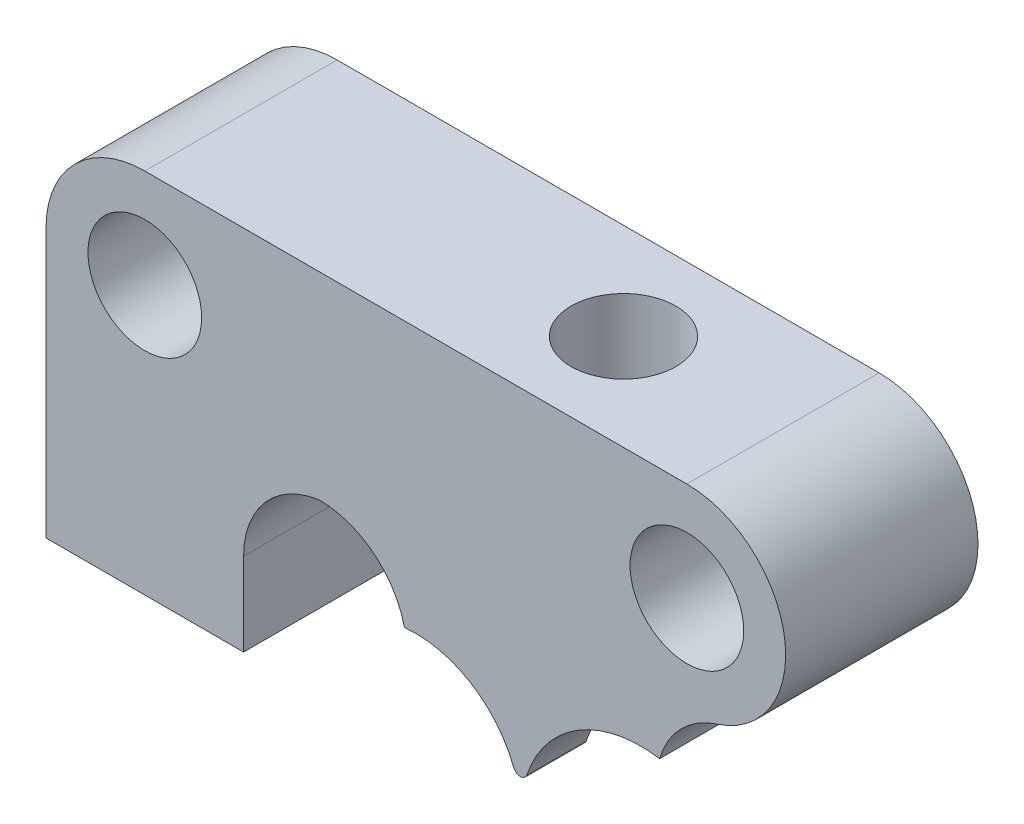
SolidWorks part; units mm, degrees
ref_plane "Front Plane" through (0, 0, 0) normal (0, 0, 1) x (1, 0, 0)
ref_plane "Top Plane" through (0, 0, 0) normal (0, 1, 0) x (1, 0, 0)
ref_plane "Right Plane" through (0, 0, 0) normal (1, 0, 0) x (0, 0, -1)
sketch "Sketch1" plane through (0, 0, 0) normal (0, 0, 1) x (1, 0, 0)
  line L0 (0, 0) -> (-15.5, 0) construction
  line L1 (0, 0) -> (0, -15.5) construction
  line L2 (-15.5, 0) -> (15.5, 0) construction
  line L3 (-15.5, 5.65) -> (15.5, 5.65)
  line L4 (-15.5, -5.65) -> (15.5, -5.65)
  circle A0 centre (-15.5, 0) radius 1.6
  circle A1 centre (15.5, 0) radius 1.6
  arc A2 (-15.5, 5.65) -> (-15.5, -5.65) centre (-15.5, 0) ccw
  arc A3 (15.5, -5.65) -> (15.5, 5.65) centre (15.5, 0) ccw
  point P7 (0, 0)
  point P12 (-21.15, 0)
  point P13 (21.15, 0)
  dimension "D4" = 3.2
  dimension "D1" = 15.5
  dimension "D2" = 15.5
  dimension "D3" = 42.3
extrude "Boss-Extrude1" add sketch "Sketch1" along normal blind 5.5 and the other way blind 5.5
sketch "Sketch3" plane through (0, 0, 0) normal (0, 0, 1) x (1, 0, 0)
  line L0 (0, 0) -> (0, -15.5) construction
  line L1 (6.375, 5.65) -> (6.375, -22.8049) construction
  line L2 (15.5, 5.65) -> (-15.5, 5.65) construction
  circle A0 centre (0, -15.5) radius 5.5
  circle A1 centre (12.85, -15.5) radius 6.3
  dimension "D2" = 11
  dimension "D3" = 1.05
  dimension "D4" = 12.6
  dimension "D6" = 0.875
  dimension "D1" = 15.5
  dimension "D5" = 12.85
sketch "Sketch4" plane through (0, 5.65, 0) normal (0, 1, 0) x (1, 0, 0)
  circle A0 centre (6.375, 0) radius 3
  dimension "D1" = 6
extrude "Cut-Extrude2" cut sketch "Sketch4" against normal blind 5 contours A0
sketch "Sketch6" plane through (0, 0, 5.5) normal (0, 0, 1) x (1, 0, 0)
  line L0 (-0.6501, -9.5353) -> (-0.6501, -5.65)
  line L1 (-15.5, -5.65) -> (15.5, -5.65) construction
  line L3 (-0.6501, -5.65) -> (13.939, -5.65)
  line L4 (13.939, -5.65) -> (13.939, -8.7371)
  arc A0 (-0.6501, -9.5353) -> (6, -15.5) centre (0, -15.5) cw
  arc A1 (6, -15.5) -> (13.939, -8.7371) centre (12.85, -15.5) cw
  circle A2 centre (0, -15.5) radius 5.5 construction
  circle A3 centre (12.85, -15.5) radius 6.3 construction
  dimension "D1" = 0.5
extrude "Boss-Extrude2" add sketch "Sketch6" against normal up to surface (11 mm away) up to face at (13.9, 0, -5.5)
fillet "Fillet1" radius 0.4 1 edges at (6, -15.5, 0)
sketch "Sketch7" plane through (0, 5.65, 0) normal (0, 1, 0) x (1, 0, 0)
  circle A0 centre (6.375, 0) radius 0.95
  dimension "D1" = 1.9
extrude "Cut-Extrude3" cut sketch "Sketch7" against normal through all
sketch "Sketch8" plane through (0, 5.65, 0) normal (0, 1, 0) x (1, 0, 0)
  circle A0 centre (6.375, 0) radius 2.1
  dimension "D1" = 4.2
extrude "Cut-Extrude5" cut sketch "Sketch8" along normal blind 10 and the other way through all from vertex starting at point (6.3529, -13.3296, 5.5)
fillet "Fillet2" radius 5 2 edges at (13.939, -5.65, 0) (-0.6501, -5.65, 0)
sketch "Sketch9" plane through (0, 0, 5.5) normal (0, 0, 1) x (1, 0, 0)
  circle A0 centre (-15.5, 0) radius 3.25
  circle A1 centre (15.5, 0) radius 3.25
  dimension "D1" = 6.5
extrude "Cut-Extrude6" cut sketch "Sketch9" against normal offset from surface (8 mm away) 3 up to face at (13.9, 0, -5.5)
sketch "Sketch10" plane through (0, 0, 5.5) normal (0, 0, 1) x (1, 0, 0)
  line L0 (-15.5, 0) -> (-15.5, -15.35) construction
  line L1 (15.5, 5.65) -> (-15.5, 5.65) construction
  line L2 (-21.15, 0) -> (-21.15, -15.35)
  line L3 (-21.15, -15.35) -> (-15.5, -15.35)
  line L4 (-9.85, -15.35) -> (-9.85, -5.65)
  line L5 (-15.5, -5.65) -> (-5.5243, -5.65) construction
  line L6 (-15.5, -5.65) -> (-5.5243, -5.65)
  line L7 (-15.5, -15.35) -> (-9.85, -15.35)
  arc A0 (-15.5, 5.65) -> (-15.5, -5.65) centre (-15.5, 0) ccw construction
  arc A1 (-15.5, 5.65) -> (-15.5, -5.65) centre (-15.5, 0) ccw
  arc M11 (-15.5, 5.65) -> (-15.5, -5.65) centre (-15.5, 0) ccw
  line M12 (-15.5, -5.65) -> (-5.5243, -5.65)
  dimension "D1" = 21
extrude "Boss-Extrude3" add sketch "Sketch10" against normal up to surface (11 mm away) contours L0 L7 L4 M12 | L0 L2 L3 M11 region at (-12.675, -10.5, 5.5) region at (-18.4987, -9.8209, 5.5) up to face at (13.9, 0, -5.5)
sketch "Sketch11" plane through (0, -15.35, 0) normal (0, -1, 0) x (1, 0, 0)
  line L0 (-15.5, 5.5) -> (-15.5, -5.5) construction
  line L1 (-9.85, -5.5) -> (-21.15, -5.5) construction
  circle A0 centre (-15.5, 0) radius 3.7
  dimension "D1" = 7.4
extrude "Cut-Extrude7" cut sketch "Sketch11" against normal blind 3
fillet "Fillet3" radius 5 1 edges at (-9.85, -5.65, 0)
